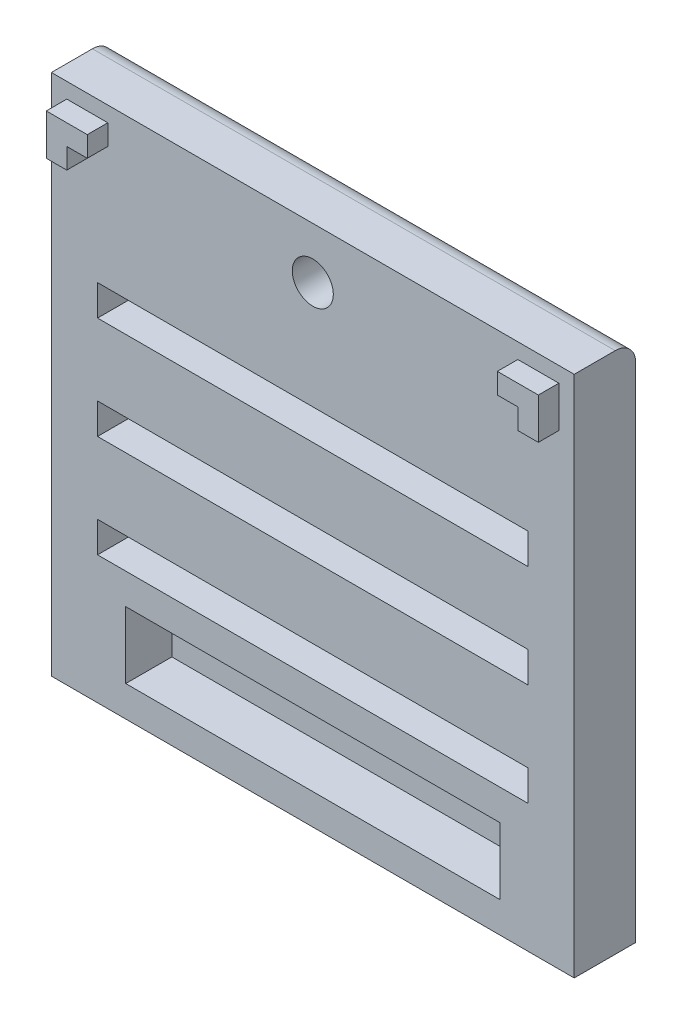
SolidWorks part; units mm, degrees
material "ABS"
ref_plane "Plano frontal" through (0, 0, 0) normal (0, 0, 1) x (1, 0, 0)
ref_plane "Plano superior" through (0, 0, 0) normal (0, 1, 0) x (1, 0, 0)
ref_plane "Plano direito" through (0, 0, 0) normal (1, 0, 0) x (0, 0, -1)
sketch "Esboço1" plane through (0, 0, 0) normal (0, 0, 1) x (1, 0, 0)
  line L1 (25.5, 25.5) -> (-25.5, 25.5)
  line L2 (25.5, 25.5) -> (25.5, -25.5)
  line L3 (25.5, -25.5) -> (-25.5, -25.5)
  line L4 (-25.5, 25.5) -> (-25.5, -25.5)
  line L5 (25.5, 25.5) -> (-25.5, -25.5) construction
  line L6 (25.5, -25.5) -> (-25.5, 25.5) construction
  point P0 (0, 0)
  dimension "D1" = 51
  dimension "D2" = 51
extrude "Ressalto-extrusão1" add sketch "Esboço1" along normal blind 6
sketch "Esboço2" plane through (0, 0, 0) normal (0, 0, -1) x (-1, 0, 0)
  line L0 (25.5, -25.5) -> (-25.5, -25.5) construction
  line L1 (-18.25, -16) -> (18.25, -16)
  line L2 (-18.25, -16) -> (-18.25, -22.5)
  line L3 (-18.25, -22.5) -> (18.25, -22.5)
  line L4 (18.25, -16) -> (18.25, -22.5)
  point P6 (0, -16)
  dimension "D1" = 36.5
  dimension "D2" = 6.5
  dimension "D3" = 3
extrude "Corte-extrusão1" cut sketch "Esboço2" against normal blind 4.5
sketch "Esboço3" plane through (0, 0, 6) normal (0, 0, 1) x (1, 0, 0)
  line L0 (25.5, 25.5) -> (-25.5, 25.5) construction
  circle A1 centre (0, 20.5) radius 2
  dimension "D1" = 4
  dimension "D2" = 5
extrude "Corte-extrusão2" cut sketch "Esboço3" against normal through all
sketch "Esboço4" plane through (0, 0, 0) normal (0, 0, -1) x (-1, 0, 0)
  line L0 (18.25, -16) -> (-18.25, -16) construction
  line L1 (-21, -10) -> (21, -10)
  line L2 (-21, -10) -> (-21, -13)
  line L3 (-21, -13) -> (21, -13)
  line L4 (21, -10) -> (21, -13)
  point P5 (0, -10)
  dimension "D1" = 3
  dimension "D2" = 3
  dimension "D3" = 42
extrude "Corte-extrusão3" cut sketch "Esboço4" against normal up to surface (4.5 mm away) up to face at (0, -19.25, 4.5)
pattern_linear "Padrão linear1" count 3 spacing 10 along (0, 1, 0) of "Corte-extrusão3"
fillet "Filete1" radius 2 1 edges at (0, 25.5, 6)
chamfer "Chanfro1" distance 1 angle 45 1 edges at (2, 20.5, 6)
sketch "Esboço5" plane through (0, 0, 0) normal (0, 0, -1) x (-1, 0, 0)
  line L0 (-25.5, -25.5) -> (-25.5, 25.5) construction
  line L1 (-24, 20) -> (-22, 20)
  line L2 (-24, 20) -> (-24, 24)
  line L3 (-24, 24) -> (-20, 24)
  line L4 (-20, 22) -> (-20, 24)
  line L5 (22, 20) -> (24, 20)
  line L6 (20, 22) -> (20, 24)
  line L7 (20, 24) -> (24, 24)
  line L8 (24, 20) -> (24, 24)
  line L11 (20, 22) -> (22, 22)
  line L12 (22, 20) -> (22, 22)
  line L15 (-20, 22) -> (-22, 22)
  line L16 (-22, 20) -> (-22, 22)
  line L17 (-25.5, 25.5) -> (25.5, 25.5) construction
  line L18 (25.5, 25.5) -> (25.5, -25.5) construction
  point P22 (-24, 22)
  point P24 (-22, 24)
  dimension "D1" = 1.5
  dimension "D2" = 1.5
  dimension "D3" = 4
  dimension "D4" = 1.5
  dimension "D5" = 4
extrude "Ressalto-extrusão2" add sketch "Esboço5" along normal blind 2
mirror "Espelhar1" about plane through (0, 0, 0) normal (0, 0, 1) of bodies 108
delete or keep bodies "Corpo-Excluir/Manter 1" type delete bodies bodies 108
